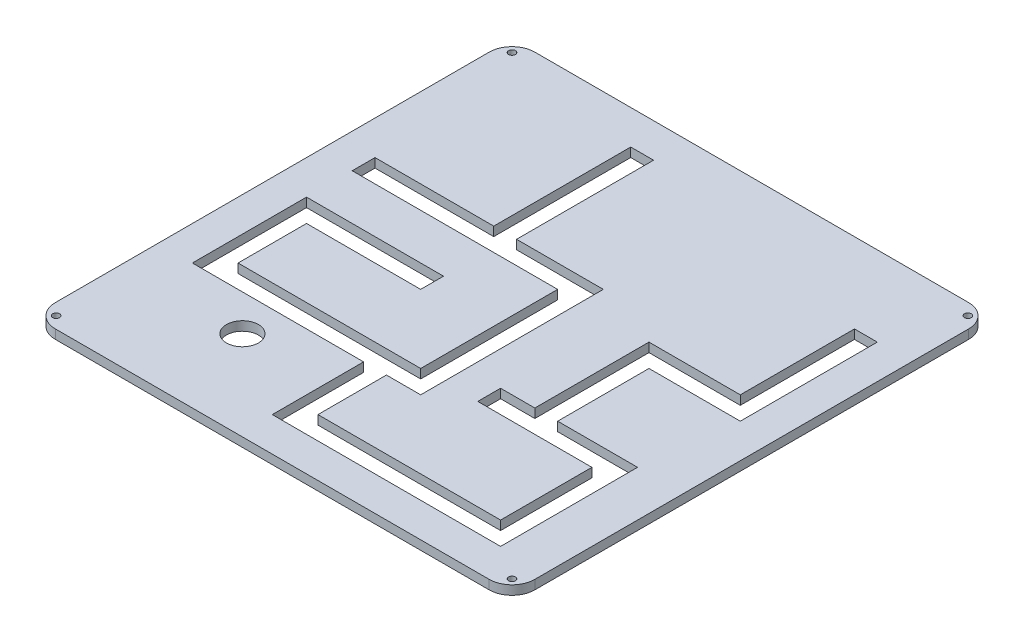
SolidWorks part; units mm, degrees
ref_plane "Front Plane" through (0, 0, 0) normal (0, 0, 1) x (1, 0, 0)
ref_plane "Top Plane" through (0, 0, 0) normal (0, 1, 0) x (1, 0, 0)
ref_plane "Right Plane" through (0, 0, 0) normal (1, 0, 0) x (0, 0, -1)
sketch "Sketch1" plane through (0, 0, 0) normal (0, 1, 0) x (1, 0, 0)
  line L0 (-101, -101) -> (-101, 101)
  line L5 (-105, -105) -> (105, -105)
  line L6 (-105, -105) -> (-105, 105)
  line L7 (-105, 105) -> (105, 105)
  line L8 (105, -105) -> (105, 105)
  line L9 (-101, 101) -> (101, 101)
  line L10 (101, -101) -> (101, 101)
  line L11 (-101, -101) -> (101, -101)
  line L12 (-101, 101) -> (-99.8333, 99.8333) construction
  line L13 (-55, 0) -> (55, 0) construction
  line L14 (-101, -101) -> (-99.8333, -99.8333) construction
  line L15 (0, -55) -> (0, 55) construction
  line L16 (101, -101) -> (99.8333, -99.8333) construction
  line L17 (101, 101) -> (99.8333, 99.8333) construction
  circle A1 centre (-99.8333, 99.8333) radius 1.5
  circle A2 centre (-99.8333, -99.8333) radius 1.5
  circle A3 centre (99.8333, -99.8333) radius 1.5
  circle A4 centre (99.8333, 99.8333) radius 1.5
  point P0 (0, 0)
  point P6 (-105, 0)
  point P7 (0, 105)
  dimension "D3" = 4
  dimension "D4" = 3
  dimension "D1" = 210
  dimension "D2" = 210
  dimension "D5" = 1.65
  dimension "D6" = 45
extrude "MainExtrude" add sketch "Sketch1" along normal blind 4 contours L6 L5 L8 L7
extrude "ScrewHoles" cut sketch "Sketch1<6>" along normal up to surface (4 mm away) contours A1 | A2 | A3 | A4 up to face at (0, 4, 0)
sketch "Sketch1<6>" plane through (0, 0, 0) normal (0, 1, 0) x (1, 0, 0) same geometry as "Sketch1"
fillet "RoundedCorners" radius 10 4 edges at (-105, 2, -105) (-105, 2, 105) (105, 2, -105) (105, 2, 105)
sketch "Sketch3" plane through (0, 0, 0) normal (0, 1, 0) x (1, 0, 0)
  line L24 (-33, 90) -> (-33, 30) construction
  line L25 (-38, 90) -> (-38, 30)
  line L58 (-90, 25) -> (5, 25) construction
  line L59 (5, 25) -> (5, -45) construction
  line L60 (5, -45) -> (-85, -45) construction
  line L61 (-85, -45) -> (-85, -5) construction
  line L62 (-85, -5) -> (-30, -5) construction
  line L63 (-10, -50) -> (-10, -85) construction
  line L64 (-10, -85) -> (80, -85) construction
  line L65 (80, -85) -> (80, -35) construction
  line L66 (80, -35) -> (25, -35) construction
  line L68 (-90, 20) -> (0, 20)
  line L69 (0, 20) -> (0, -40)
  line L70 (0, -40) -> (-80, -40)
  line L71 (-80, -40) -> (-80, -10)
  line L72 (-80, -10) -> (-30, -10)
  line L73 (-15, -50) -> (-15, -90)
  line L74 (-15, -90) -> (85, -90)
  line L75 (85, -90) -> (85, -30)
  line L76 (85, -30) -> (50, -30)
  line L77 (-28, 90) -> (-28, 30)
  line L78 (-90, 30) -> (-38, 30)
  line L79 (10, 30) -> (10, -50)
  line L80 (10, -50) -> (-5, -50)
  line L81 (-90, -50) -> (-90, 0)
  line L82 (-90, 0) -> (-30, 0)
  line L83 (-5, -50) -> (-5, -80)
  line L84 (-5, -80) -> (75, -80)
  line L85 (75, -80) -> (75, -40)
  line L86 (75, -40) -> (25, -40)
  line L87 (-38, 90) -> (-28, 90)
  line L89 (-90, 20) -> (-90, 30)
  line L90 (-30, -10) -> (-30, 0)
  line L92 (25, -30) -> (25, -40)
  line L93 (-28, 90) -> (-28, 12.6574) construction
  line L94 (-33, 90) -> (-33, 12.6574) construction
  line L95 (-38, 90) -> (-38, 12.6574) construction
  line L96 (-5, 27.5948) -> (-5, -80) construction
  line L97 (-10, 27.5948) -> (-10, -85) construction
  line L98 (-15, 27.5948) -> (-15, -90) construction
  line L99 (-15, -50) -> (-90, -50)
  line L100 (10, -50) -> (-90, -50) construction
  line L101 (-28, 30) -> (10, 30)
  line L102 (-90, 30) -> (10, 30) construction
  line L106 (45, -30) -> (45, 15) construction
  line L107 (45, 15) -> (85, 15) construction
  line L108 (85, 15) -> (85, 70) construction
  line L109 (50, -30) -> (50, 10)
  line L110 (50, 10) -> (90, 10)
  line L111 (-12.3092, 87.9178) -> (68.6908, 87.9178) construction
  line L112 (-12.3092, 87.9178) -> (-12.3092, 44.9178) construction
  line L113 (-12.3092, 44.9178) -> (68.6908, 44.9178) construction
  line L114 (68.6908, 87.9178) -> (68.6908, 44.9178) construction
  line L115 (90, 10) -> (90, 70)
  line L116 (40, -30) -> (40, 20)
  line L117 (40, 20) -> (80, 20)
  line L118 (80, 20) -> (80, 70)
  line L120 (90, 70) -> (80, 70)
  line L121 (40, -30) -> (25, -30)
  line L122 (85, -30) -> (25, -30) construction
  line L123 (105, -95) -> (105, 95) construction
  line L124 (-105, -95) -> (-105, 95) construction
  line L125 (-95, 105) -> (95, 105) construction
  line L126 (-95, -105) -> (95, -105) construction
  circle A1 centre (-52.2057, -65.8684) radius 7
  dimension "D18" = 14
  dimension "D1" = 5
  dimension "D2" = 5
  dimension "D3" = 60
  dimension "D4" = 5
  dimension "D5" = 5
  dimension "D6" = 40
  dimension "D7" = 60
  dimension "D8" = 100
  dimension "D9" = 60
  dimension "D11" = 60
  dimension "D13" = 30
  dimension "D14" = 100
  dimension "D10" = 30
  dimension "D12" = 40
  dimension "D15" = 50
  dimension "D17" = 100
  dimension "D16" = 50
  dimension "D19" = 43
  dimension "D20" = 81
  dimension "D21" = 15
  dimension "D22" = 15
  dimension "D23" = 15
  dimension "D24" = 15
  dimension "D25" = 15
  dimension "D26" = 108
extrude "Trench" cut sketch "Sketch3" along normal blind 4
